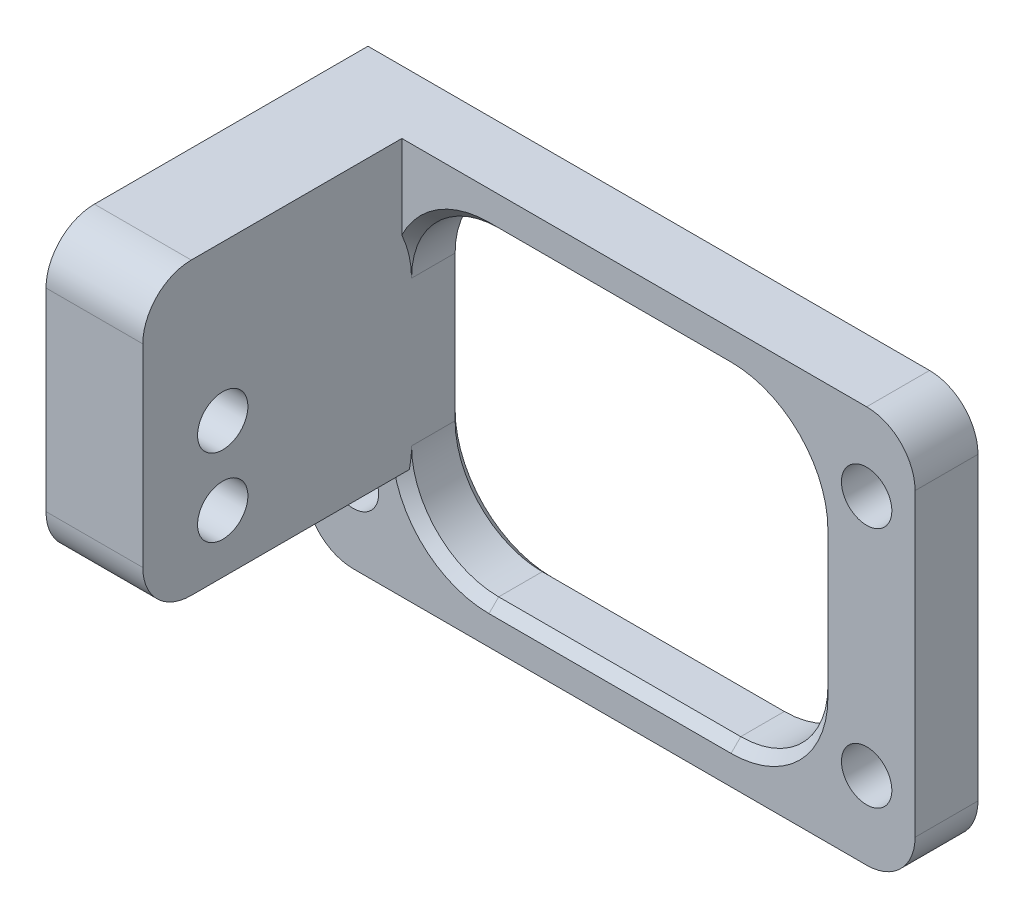
SolidWorks part; units mm, degrees
ref_plane "Front Plane" through (0, 0, 0) normal (0, 0, 1) x (1, 0, 0)
ref_plane "Top Plane" through (0, 0, 0) normal (0, 1, 0) x (1, 0, 0)
ref_plane "Right Plane" through (0, 0, 0) normal (1, 0, 0) x (0, 0, -1)
sketch "Sketch1" plane through (0, 0, 0) normal (0, 0, 1) x (1, 0, 0)
  line L0 (39, -5) -> (14, -5) construction
  line L1 (14, 29) -> (39, 29)
  line L2 (5, 20) -> (5, 5)
  line L3 (14, -4) -> (39, -4)
  line L4 (48, 20) -> (48, 5)
  line L5 (-5, 33) -> (53, 33)
  line L6 (-5, 33) -> (-5, -3)
  line L7 (0, -8) -> (53, -8)
  line L8 (58, 28) -> (58, -3)
  line L9 (4, 5) -> (4, 20) construction
  line L10 (49, 20) -> (49, 5) construction
  line L11 (14, 30) -> (39, 30) construction
  arc A0 (39, -4) -> (48, 5) centre (39, 5) ccw
  arc A1 (39, 29) -> (48, 20) centre (39, 20) cw
  arc A2 (14, 29) -> (5, 20) centre (14, 20) ccw
  arc A3 (5, 5) -> (14, -4) centre (14, 5) ccw
  circle A4 centre (0, 0) radius 2.6
  circle A5 centre (53, 0) radius 2.6
  circle A6 centre (53, 25) radius 2.6
  arc A7 (53, 33) -> (58, 28) centre (53, 28) cw
  arc A8 (53, -8) -> (58, -3) centre (53, -3) ccw
  arc A9 (-5, -3) -> (0, -8) centre (0, -3) ccw
  dimension "D1" = 9
  dimension "D2" = 5.2
  dimension "D11" = 5
  dimension "D3" = 1
  dimension "D4" = 1
  dimension "D5" = 1
  dimension "D6" = 1
  dimension "D7" = 10
  dimension "D8" = 4
  dimension "D9" = 4
  dimension "D10" = 10
extrude "Boss-Extrude1" add sketch "Sketch1" along normal blind 6.5
sketch "Sketch3" plane through (-5, 0, 0) normal (-1, 0, 0) x (0, 0, 1)
  line L1 (6.5, 33) -> (28.25, 33)
  line L2 (6.5, 33) -> (6.5, 3)
  line L3 (6.5, 3) -> (28.25, 3)
  line L4 (33.25, 28) -> (33.25, 8)
  line L5 (0, 33) -> (0, -3) construction
  circle A0 centre (25, 17) radius 2.6
  circle A1 centre (25, 9) radius 2.6
  arc A2 (28.25, 33) -> (33.25, 28) centre (28.25, 28) cw
  arc A3 (28.25, 3) -> (33.25, 8) centre (28.25, 8) ccw
  point P13 (33.25, 33)
  point P16 (33.25, 3)
  dimension "D3" = 5.2
  dimension "D7" = 5
  dimension "D1" = 6
  dimension "D2" = 8
  dimension "D4" = 25
  dimension "D5" = 8.25
  dimension "D6" = 30
extrude "Boss-Extrude2" add sketch "Sketch3" against normal blind 10
chamfer "Chamfer1" distance 1 angle 45 15 edges at (7.636, -1.364, 0) (26.5, -4, 0) (5, 12.5, 0) (45.364, -1.364, 0) (7.636, 26.364, 0) (48, 12.5, 0) (26.5, 29, 0) (45.364, 26.364, 0) (26.5, -4, 6.5) (45.364, -1.364, 6.5) (48, 12.5, 6.5) (45.364, 26.364, 6.5) (26.5, 29, 6.5)
